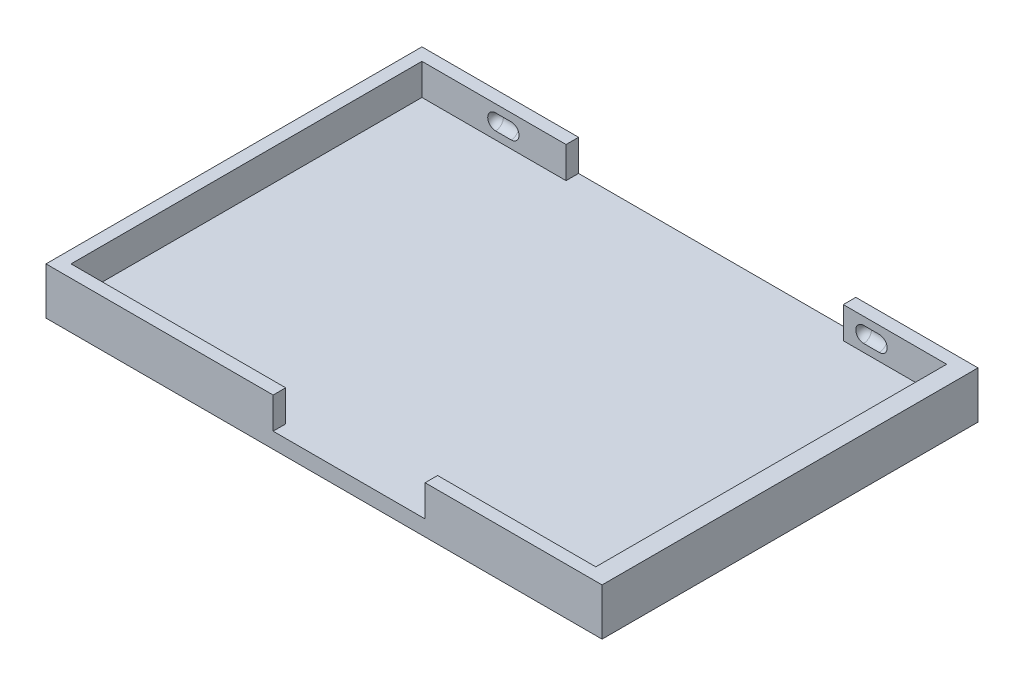
SolidWorks part; units mm, degrees
ref_plane "前视基准面" through (0, 0, 0) normal (0, 0, 1) x (1, 0, 0)
ref_plane "上视基准面" through (0, 0, 0) normal (0, 1, 0) x (1, 0, 0)
ref_plane "右视基准面" through (0, 0, 0) normal (1, 0, 0) x (0, 0, -1)
sketch "草图1" plane through (0, 0, 0) normal (0, 1, 0) x (1, 0, 0)
  line L1 (-17.75, 12) -> (17.75, 12)
  line L2 (-17.75, 12) -> (-17.75, -12)
  line L3 (-17.75, -12) -> (17.75, -12)
  line L4 (17.75, 12) -> (17.75, -12)
  line L5 (-17.75, 12) -> (17.75, -12) construction
  line L6 (-17.75, -12) -> (17.75, 12) construction
  point P0 (0, 0)
  dimension "D1" = 24
  dimension "D2" = 35.5
extrude "凸台-拉伸1" add sketch "草图1" along normal blind 3
sketch "草图2" plane through (0, 3, 0) normal (0, 1, 0) x (1, 0, 0)
  line L1 (-16.95, 11.2) -> (16.55, 11.2)
  line L2 (-16.95, 11.2) -> (-16.95, -11.2)
  line L3 (-16.95, -11.2) -> (16.55, -11.2)
  line L4 (16.55, 11.2) -> (16.55, -11.2)
  line L5 (-16.95, 11.2) -> (16.55, -11.2) construction
  line L6 (-16.95, -11.2) -> (16.55, 11.2) construction
  line L7 (-17.75, 12) -> (-17.75, -12) construction
  line L8 (17.75, -12) -> (17.75, 12) construction
  line L9 (17.75, 12) -> (-17.75, 12) construction
  line L10 (-17.75, -12) -> (17.75, -12) construction
  point P0 (0, 0)
  dimension "D1" = 0.8
  dimension "D2" = 0.8
  dimension "D3" = 1.2
  dimension "D4" = 0.8
extrude "切除-拉伸1" cut sketch "草图2" against normal blind 2
sketch "草图4" plane through (0, 3, 0) normal (0, 1, 0) x (1, 0, 0)
  line L0 (-16.95, -11.2) -> (16.55, -11.2) construction
  line L1 (-3.25, -11.2) -> (6.45, -11.2)
  line L2 (-3.25, -11.2) -> (-3.25, -12)
  line L3 (-3.25, -12) -> (6.45, -12)
  line L4 (6.45, -11.2) -> (6.45, -12)
  line L5 (-17.75, -12) -> (17.75, -12) construction
  line L6 (17.75, -12) -> (17.75, 12) construction
  line L7 (-17.75, 12) -> (-17.75, -12) construction
  dimension "D1" = 11.3
  dimension "D2" = 14.5
extrude "切除-拉伸2" cut sketch "草图4" against normal blind 2
sketch "草图5" plane through (0, 3, 0) normal (0, 1, 0) x (1, 0, 0)
  line L0 (17.75, 12) -> (-17.75, 12) construction
  line L1 (-7.75, 12) -> (9.95, 12)
  line L2 (-7.75, 12) -> (-7.75, 11.2)
  line L3 (-7.75, 11.2) -> (9.95, 11.2)
  line L4 (9.95, 12) -> (9.95, 11.2)
  line L5 (16.55, 11.2) -> (-16.95, 11.2) construction
  line L6 (17.75, -12) -> (17.75, 12) construction
  line L7 (-17.75, 12) -> (-17.75, -12) construction
  dimension "D1" = 7.8
  dimension "D2" = 10
extrude "切除-拉伸3" cut sketch "草图5" against normal blind 2
sketch "草图6" plane through (0, 0, 11.2) normal (0, 0, -1) x (-1, 0, 0)
  line L0 (-9.386, 2) -> (-11.386, 2)
  line L2 (-6.45, 3) -> (-16.55, 3) construction
  line L3 (9.75, 2) -> (11.75, 2)
  line L4 (10.25, 2.5) -> (11.25, 2.5)
  line L6 (17.75, 3) -> (17.75, 0) construction
  line L7 (-10.886, 2.5) -> (-9.886, 2.5)
  arc A2 (10.25, 2.5) -> (9.75, 2) centre (10.25, 2) ccw
  arc A3 (11.25, 2.5) -> (11.75, 2) centre (11.25, 2) cw
  arc A4 (-10.886, 2.5) -> (-11.386, 2) centre (-10.886, 2) ccw
  arc A5 (-9.886, 2.5) -> (-9.386, 2) centre (-9.886, 2) cw
  point P4 (-10.386, 2.5)
  point P13 (10.75, 2.5)
  point P14 (10.75, 2)
  point P17 (-10.386, 2)
  dimension "D2" = 1
  dimension "D4" = 2
  dimension "D1" = 2
  dimension "D3" = 1
  dimension "D5" = 1
  dimension "D6" = 6
  dimension "D7" = 0.5
revolve "切除-旋转1" cut sketch "草图6" angle 360 about L0
sketch "草图7" plane through (0, 0, -11.2) normal (0, 0, 1) x (1, 0, 0)
  line L0 (-10.75, 2) -> (-12.75, 2)
  line L1 (10.75, 2) -> (12.75, 2)
  line L3 (-7.75, 3) -> (-16.95, 3) construction
  line L4 (-11.25, 2.5) -> (-12.25, 2.5)
  line L6 (-17.75, 3) -> (-17.75, 0) construction
  line L7 (12.25, 2.5) -> (11.25, 2.5)
  line L8 (17.75, 3) -> (17.75, 0) construction
  arc A2 (-11.25, 2.5) -> (-10.75, 2) centre (-11.25, 2) cw
  arc A3 (-12.25, 2.5) -> (-12.75, 2) centre (-12.25, 2) ccw
  arc A4 (12.25, 2.5) -> (12.75, 2) centre (12.25, 2) cw
  arc A5 (11.25, 2.5) -> (10.75, 2) centre (11.25, 2) ccw
  point P6 (-11.75, 2.5)
  point P7 (-11.75, 2)
  point P16 (11.75, 2.5)
  point P17 (11.75, 2)
  dimension "D1" = 2
  dimension "D4" = 0.5
  dimension "D2" = 1
  dimension "D3" = 1
  dimension "D5" = 5
  dimension "D6" = 2
  dimension "D7" = 1
  dimension "D8" = 5
revolve "切除-旋转2" cut sketch "草图7" angle 360 about L0
